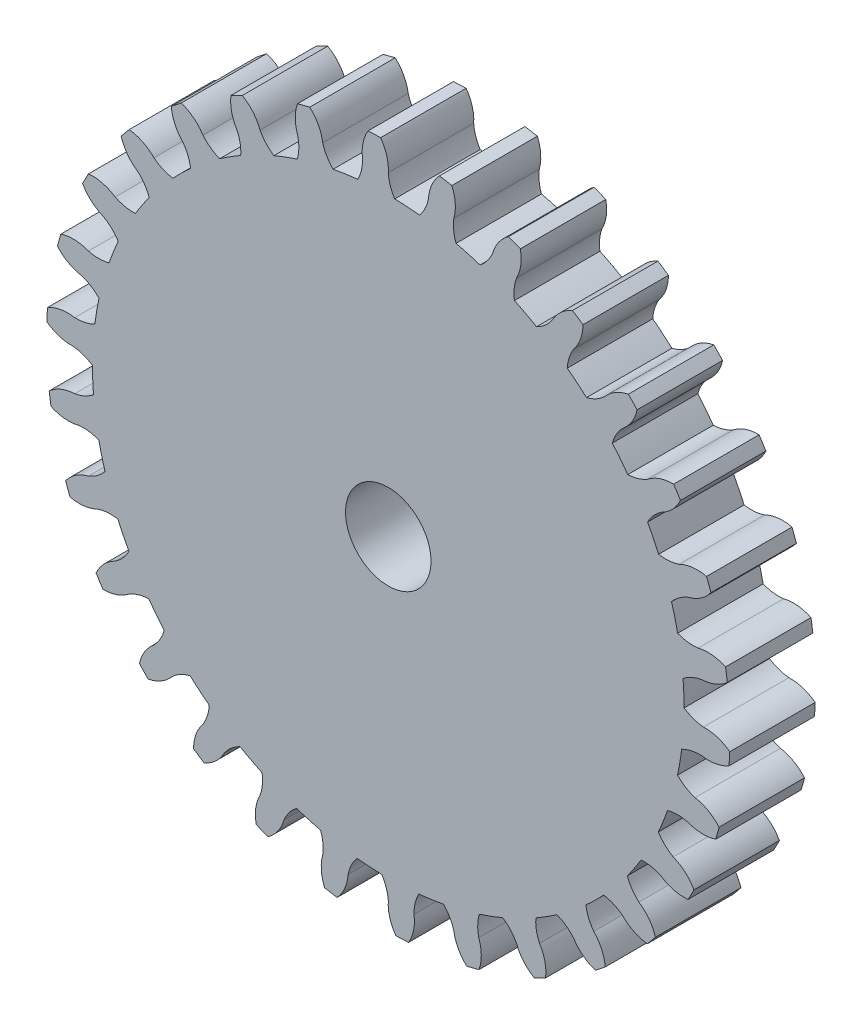
SolidWorks part; units mm, degrees
ref_plane "Alzado" through (0, 0, 0) normal (0, 0, 1) x (1, 0, 0)
ref_plane "Planta" through (0, 0, 0) normal (0, 1, 0) x (1, 0, 0)
ref_plane "Vista lateral" through (0, 0, 0) normal (1, 0, 0) x (0, 0, -1)
sketch "Croquis1" plane through (0, 0, 0) normal (0, 0, 1) x (1, 0, 0)
  circle A0 centre (0, 0) radius 43.9547
  circle A1 centre (0, 0) radius 47.625
  circle A2 centre (0, 0) radius 50.8
  circle A3 centre (0, 47.625) radius 6.0833
  circle A4 centre (-6.0709, 47.2365) radius 6.0833
  circle A5 centre (6.0709, 47.2365) radius 6.0833
  circle A6 centre (12.0427, 46.0773) radius 6.0833
  dimension "D1" = 101.6
  dimension "D2" = 95.25
  dimension "D3" = 87.9094
  dimension "D4" = 12.1666
extrude "Saliente-Extruir1" add sketch "Croquis1" along normal blind 12.7 contours A2
extrude "Cortar-Extruir1" cut sketch "Croquis1<4>" along normal through all contours A6 A2 A3 | A2 A5 A1 A3 | A5 A2 A4 | A6 A1 A4 A5 A0 A3 region at (2.9312, 45.8018, 0) region at (3.1357, 48.9981, 0) region at (6.3671, 49.5414, 0) region at (0, 49.9489, 0)
sketch "Croquis1<4>" plane through (0, 0, 0) normal (0, 0, 1) x (1, 0, 0) same geometry as "Croquis1"
pattern_circular "MatrizC1" count 30 over 360 about axis through (0, 0, 12.7) along (0, 0, 1) of "Cortar-Extruir1"
sketch "Croquis2" plane through (0, 0, 12.7) normal (0, 0, 1) x (1, 0, 0)
  circle A0 centre (0, 0) radius 6.35
  dimension "D1" = 12.7
extrude "Cortar-Extruir2" cut sketch "Croquis2" against normal through all
